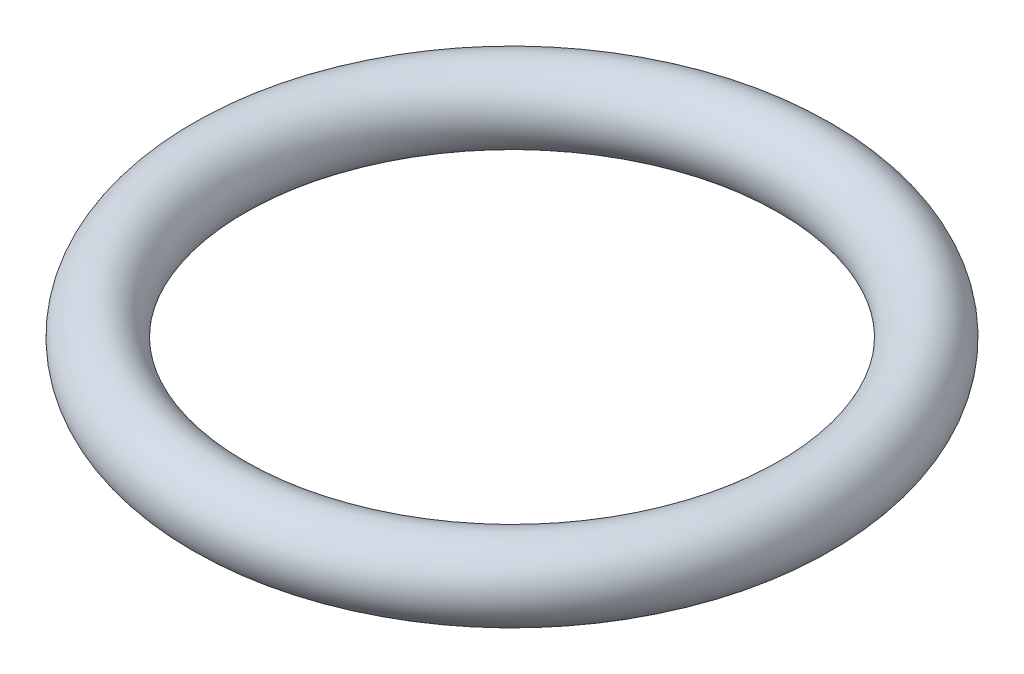
SolidWorks part; units mm, degrees
ref_plane "Front" through (0, 0, 0) normal (0, 0, 1) x (1, 0, 0)
ref_plane "Top" through (0, 0, 0) normal (0, 1, 0) x (1, 0, 0)
ref_plane "Right" through (0, 0, 0) normal (1, 0, 0) x (0, 0, -1)
sketch "Sketch1" plane through (0, 0, 0) normal (0, 0, 1) x (1, 0, 0)
  line L0 (0, 14.0803) -> (0, -13.5453) construction
  line L1 (-13.2918, 0) -> (15.7418, 0) construction
  circle A0 centre (-10, 0) radius 1.25
  dimension "D1" = 2.5
  dimension "D2" = 10
revolve "Revolve1" add sketch "Sketch1" angle 360 about L0
ref_axis "Axis1" through (0, 4.752, 0) along (0, -1, 0)
